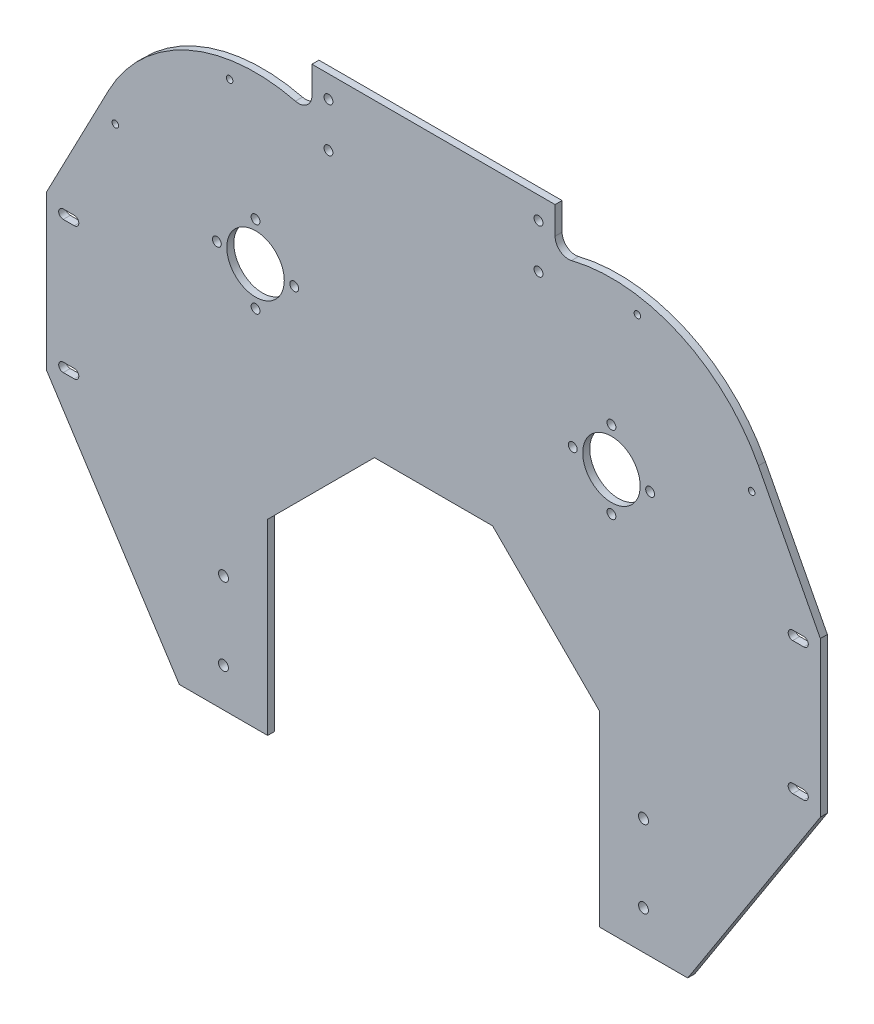
SolidWorks part; units mm, degrees
ref_plane "Front Plane" through (0, 0, 0) normal (0, 0, 1) x (1, 0, 0)
ref_plane "Top Plane" through (0, 0, 0) normal (0, 1, 0) x (1, 0, 0)
ref_plane "Right Plane" through (0, 0, 0) normal (1, 0, 0) x (0, 0, -1)
sketch "Sketch1" plane through (0, 0, 0) normal (0, 0, 1) x (1, 0, 0)
  line L1 (-100, -75) -> (100, -75)
  line L2 (-100, -75) -> (-100, 75)
  line L3 (-100, 75) -> (100, 75)
  line L4 (100, -75) -> (100, 75)
  line L5 (-100, -75) -> (100, 75) construction
  line L6 (-100, 75) -> (100, -75) construction
  line L8 (-47.5, 40) -> (47.5, 40) construction
  line L9 (0, 75) -> (0, -75) construction
  line L10 (-27, -44) -> (27, -44) construction
  line L11 (-27, -44) -> (-27, 28) construction
  line L12 (-27, 28) -> (27, 28) construction
  line L13 (27, -44) -> (27, 28) construction
  line L14 (-27, -44) -> (27, 28) construction
  line L15 (-27, 28) -> (27, -44) construction
  line L23 (-55, 70) -> (55, 70)
  line L24 (-55, 70) -> (-55, -70)
  line L25 (-55, -70) -> (55, -70)
  line L26 (55, 70) -> (55, -70)
  line L27 (-55, 70) -> (55, -70) construction
  line L28 (-55, -70) -> (55, 70) construction
  line L29 (-32.5, 70) -> (32.5, 70) construction
  line L30 (-32.5, 70) -> (-32.5, 55) construction
  line L31 (-32.5, 55) -> (32.5, 55) construction
  line L32 (32.5, 70) -> (32.5, 55) construction
  line L33 (-32.5, 70) -> (32.5, 55) construction
  line L34 (-32.5, 55) -> (32.5, 70) construction
  circle A2 centre (-47.5, 40) radius 2
  circle A3 centre (47.5, 40) radius 2
  circle A4 centre (-27, 28) radius 2 construction
  circle A5 centre (27, 28) radius 2 construction
  circle A6 centre (27, -44) radius 2 construction
  circle A7 centre (-27, -44) radius 2 construction
  circle A8 centre (-47.5, 60) radius 2
  circle A10 centre (47.5, 60) radius 2
  point P0 (0, 0)
  point P15 (0, 40)
  point P18 (0, -8)
  point P56 (0, 0)
  point P63 (0, 62.5)
  dimension "D3" = 4
  dimension "D4" = 20
  dimension "D5" = 4
  dimension "D8" = 4
  dimension "D1" = 150
  dimension "D2" = 200
  dimension "D6" = 72
  dimension "D7" = 54
  dimension "D14" = 30
  dimension "D15" = 140
  dimension "D16" = 110
  dimension "D17" = 95
  dimension "D18" = 12
  dimension "D19" = 15
  dimension "D20" = 65
extrude "Boss-Extrude1" add sketch "Sketch1" along normal blind 3.175 contours L23 L32 L31 L30 L24 L25 L26 A7 A6 A5 A4 A3 A2 region at (0, -0.1637, 0)
sketch "Sketch2" plane through (0, 0, 0) normal (0, 0, 1) x (1, 0, 0)
  line L0 (-55, -70) -> (-100.8579, -115.8579) construction
  line L1 (-55, 70) -> (-55, -70) construction
  line L2 (-55, -41.7157) -> (-115, -101.7157)
  line L3 (-26.7157, -70) -> (-86.7157, -130)
  line L4 (-55, -70) -> (55, -70) construction
  line L5 (-115, -101.7157) -> (-86.7157, -130)
  line L6 (-115, -101.7157) -> (-115, -203)
  line L7 (-75, -118.2843) -> (-75, -203)
  line L8 (-75, -203) -> (-115, -203)
  line L9 (0, 75) -> (0, -75) construction
  line L10 (-55, -41.7157) -> (-26.7157, -70)
  line L11 (-55, 70) -> (-55, -70) construction
  line L12 (-115, -203) -> (-66.3325, -203) construction
  circle A0 centre (-95, -150.5) radius 2.25
  circle A1 centre (-95, -185.5) radius 2.25
  circle A2 centre (-95, -150.5) radius 2.25 construction
  circle A4 centre (-95, -185.5) radius 2.25 construction
  dimension "D1" = 135
  dimension "D2" = 40
  dimension "D3" = 40
  dimension "D4" = 75
  dimension "D5" = 0
extrude "Boss-Extrude2" add sketch "Sketch2" along normal blind 3.175 contours L8 L7 L3 L5 L6 | L10 L2 L5 L3 region at (-70.8579, -85.8579, 0) region at (-95.9307, -160.1869, 0)
mirror "Mirror1" about plane through (0, 0, 0) normal (1, 0, 0) of "Boss-Extrude2"
sketch "Sketch3" plane through (0, 0, 3.175) normal (0, 0, 1) x (1, 0, 0)
  line L0 (0, 31.3301) -> (0, 52.1198) construction
  line L1 (-80.5, -21) -> (-92.2213, 45.4745) construction
  line L2 (-80.5, -21) -> (80.5, -21) construction
  line L3 (-80.5, -21) -> (-148, -21) construction
  line L4 (-80.5, -21) -> (-143.9293, 2.0864) construction
  circle A0 centre (-80.5, -21) radius 75
  circle A1 centre (-80.5, -3.5) radius 2
  circle A2 centre (80.5, -21) radius 75
  circle A3 centre (-80.5, -21) radius 60
  circle A4 centre (80.5, -21) radius 60
  circle A5 centre (-47.5, 40) radius 2 construction
  circle A6 centre (-47.5, 40) radius 2
  circle A7 centre (47.5, 40) radius 2
  circle A8 centre (-63, -21) radius 2
  circle A9 centre (-80.5, -38.5) radius 2
  circle A10 centre (-98, -21) radius 2
  circle A11 centre (98, -21) radius 2
  circle A12 centre (80.5, -38.5) radius 2
  circle A13 centre (63, -21) radius 2
  circle A14 centre (80.5, -3.5) radius 2
  circle A15 centre (-80.5, -21) radius 13
  circle A16 centre (80.5, -21) radius 13
  circle A17 centre (-92.2213, 45.4745) radius 1.4732
  circle A18 centre (-143.9293, 2.0864) radius 1.4732
  circle A19 centre (-80.5, -21) radius 67.5 construction
  circle A20 centre (92.2213, 45.4745) radius 1.4732
  circle A21 centre (143.9293, 2.0864) radius 1.4732
  point P28 (-80.5, -21)
  line M3 (115, -101.7157) -> (55, -41.7157)
  line M4 (55, -41.7157) -> (55, 70)
  line M6 (-55, 70) -> (-55, -41.7157)
  line M7 (-55, -41.7157) -> (-115, -101.7157)
  line M11 (-75, -118.2843) -> (-26.7157, -70)
  line M12 (-26.7157, -70) -> (26.7157, -70)
  line M13 (26.7157, -70) -> (75, -118.2843)
  circle M17 centre (-47.5, 40) radius 2
  circle M18 centre (47.5, 40) radius 2
  dimension "D1" = 161
  dimension "D2" = 150
  dimension "D3" = 61
  dimension "D4" = 120
  dimension "D5" = 4
  dimension "D7" = 35
  dimension "D8" = 26
  dimension "D9" = 7.5
  dimension "D10" = 2.9464
  dimension "D6" = 4
  dimension "D11" = 80
  dimension "D12" = 20
extrude "Boss-Extrude3" add sketch "Sketch3" against normal up to surface (3.175 mm away) contours A3 M6 M7 | A3 A0 M6 M7 | A3 A0 M7 M11 M12 M6 M17 | A3 M7 M6 | A4 M3 M4 | A4 M4 M3 | A4 A2 M4 M3 | A4 A2 M3 M4 M12 M13 M18 region at (-11.8554, -46.5242, 3.175) region at (9.6495, -2.4591, 3.175) region at (-56.7712, 41.4218, 3.175) region at (-96.2806, -16.4848, 3.175) region at (-46.5969, -30.7004, 3.175) region at (122.5668, 38.9404, 3.175) region at (46.5969, -30.7004, 3.175) region at (96.2806, -16.4848, 3.175) up to face at (0, -95.388, 0)
sketch "Sketch4" plane through (0, 0, 3.175) normal (0, 0, 1) x (1, 0, 0)
  line L0 (-175, -75) -> (-100, -75) construction
  line L1 (-100, -40) -> (-153.0534, -40)
  line L2 (-100, -40) -> (-100, -110)
  line L3 (-100, -110) -> (-115, -110) construction
  line L4 (-175, -40) -> (-175, -110)
  line L5 (-100, -40) -> (-175, -110) construction
  line L6 (-100, -110) -> (-175, -40) construction
  line L7 (-175, -110) -> (-115, -203)
  line L9 (-115, -101.7157) -> (-115, -203) construction
  line L10 (-115, -110) -> (-115, -203)
  line L11 (-175, -40) -> (-146.9976, 13.6853)
  line L12 (-153.0534, -40) -> (-175, -40)
  line L13 (-100, -110) -> (-115, -110) construction
  line L14 (-100, -110) -> (-100, -101.7157)
  line L15 (-100, -101.7157) -> (-115, -101.7157)
  line L16 (-115, -110) -> (-115, -101.7157)
  line L17 (-100, -110) -> (-115, -101.7157) construction
  line L18 (-100, -101.7157) -> (-115, -110) construction
  line L19 (-151.1989, -110) -> (-175, -110) construction
  line L21 (-165, -75) -> (-165, -40) construction
  line L22 (-162.5, -45) -> (-167.5, -45) construction
  line L23 (-162.5, -47.05) -> (-167.5, -47.05)
  line L24 (-162.5, -42.95) -> (-167.5, -42.95)
  line L25 (-162.5, -105) -> (-167.5, -105) construction
  line L26 (-162.5, -102.95) -> (-167.5, -102.95)
  line L27 (-162.5, -107.05) -> (-167.5, -107.05)
  arc A0 (-55, 49.5319) -> (-105.1261, -91.8418) centre (-80.5, -21) ccw construction
  arc A1 (-146.9976, 13.6853) -> (-153.0534, -40) centre (-80.5, -21) ccw
  circle A2 centre (-165, -45) radius 2.05 construction
  arc A3 (-162.5, -47.05) -> (-162.5, -42.95) centre (-162.5, -45) ccw
  arc A4 (-167.5, -42.95) -> (-167.5, -47.05) centre (-167.5, -45) ccw
  arc A5 (-162.5, -102.95) -> (-162.5, -107.05) centre (-162.5, -105) cw
  arc A6 (-167.5, -107.05) -> (-167.5, -102.95) centre (-167.5, -105) cw
  point P4 (-137.5, -75)
  point P23 (-107.5, -105.8579)
  point P32 (-165, -45)
  point P37 (-115, -111.6105)
  point P40 (-165, -105)
  arc M12 (-55, 49.5319) -> (-105.1261, -91.8418) centre (-80.5, -21) ccw
  line M13 (-105.1261, -91.8418) -> (-115, -101.7157)
  line M14 (-115, -101.7157) -> (-115, -203)
  circle M41 centre (-143.9293, 2.0864) radius 1.4732
  dimension "D7" = 4.1
  dimension "D8" = 2.05
  dimension "D1" = 40
  dimension "D2" = 100
  dimension "D3" = 70
  dimension "D4" = 75
  dimension "D6" = 10
  dimension "D9" = 5
  dimension "D10" = 5
extrude "Boss-Extrude5" add sketch "Sketch4" against normal up to surface (3.175 mm away) contours L16 L12 L4 L7 A4 L24 A3 L23 L27 A6 L26 A5 M13 M12 M14 | L15 L14 L2 L1 M12 M13 M41 | L12 L11 M12 region at (-120.1023, -62.6792, 3.175) region at (-142.6858, -110.2719, 3.175) region at (-161.1873, -26.2241, 3.175) up to face at (0, -80.3864, 0)
mirror "Mirror2" about plane through (0, 0, 0) normal (1, 0, 0) of "Boss-Extrude5"
fillet "Fillet1" radius 6 2 edges at (55, 49.5319, 1.5875) (-55, 49.5319, 1.5875)
